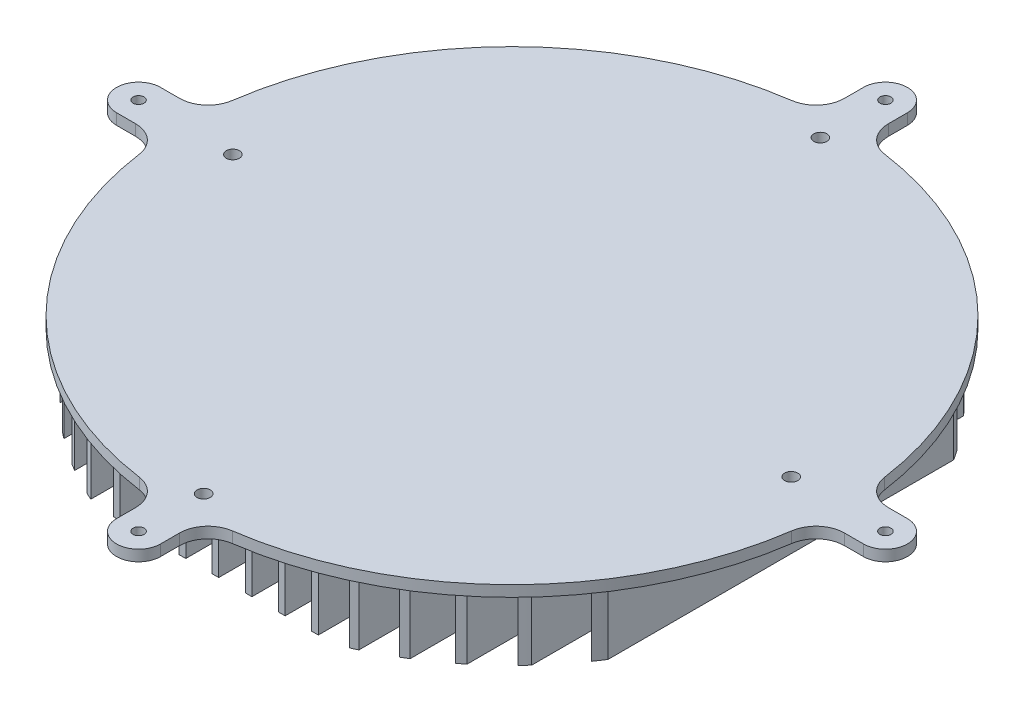
SolidWorks part; units mm, degrees
material "1060 Alloy"
ref_plane "Front Plane" through (0, 0, 0) normal (0, 0, 1) x (1, 0, 0)
ref_plane "Top Plane" through (0, 0, 0) normal (0, 1, 0) x (1, 0, 0)
ref_plane "Right Plane" through (0, 0, 0) normal (1, 0, 0) x (0, 0, -1)
sketch "Sketch3" plane through (0, 0, 0) normal (0, 1, 0) x (1, 0, 0)
  line L0 (0, 0) -> (211.9111, 0) construction
  line L1 (0, 0) -> (-205.2426, 0) construction
  line L2 (0, 0) -> (0, 170) construction
  line L3 (0, 0) -> (0, -200) construction
  line L4 (161.3691, 10) -> (170, 10)
  line L5 (161.3691, -10) -> (170, -10)
  line L6 (-10, 161.3691) -> (-10, 170)
  line L7 (10, 161.3691) -> (10, 170)
  line L8 (10, -161.3691) -> (10, -170)
  line L9 (-10, -161.3691) -> (-10, -170)
  line L10 (-161.3691, -10) -> (-170, -10)
  line L11 (-161.3691, 10) -> (-170, 10)
  arc A0 (-21.1656, 148.4992) -> (-148.4992, 21.1656) centre (0, 0) ccw
  circle A1 centre (0, 170) radius 2.5
  arc A2 (-10, 170) -> (10, 170) centre (0, 170) cw
  arc A3 (10, 161.3691) -> (21.1656, 148.4992) centre (23, 161.3691) ccw
  arc A4 (-10, 161.3691) -> (-21.1656, 148.4992) centre (-23, 161.3691) cw
  arc A5 (170, 10) -> (170, -10) centre (170, 0) cw
  arc A6 (161.3691, 10) -> (148.4992, 21.1656) centre (161.3691, 23) cw
  circle A7 centre (170, 0) radius 2.5
  arc A8 (161.3691, -10) -> (148.4992, -21.1656) centre (161.3691, -23) ccw
  arc A9 (10, -170) -> (-10, -170) centre (0, -170) cw
  arc A10 (10, -161.3691) -> (21.1656, -148.4992) centre (23, -161.3691) cw
  circle A11 centre (0, -170) radius 2.5
  arc A12 (-10, -161.3691) -> (-21.1656, -148.4992) centre (-23, -161.3691) ccw
  arc A13 (-170, -10) -> (-170, 10) centre (-170, 0) cw
  arc A14 (-161.3691, -10) -> (-148.4992, -21.1656) centre (-161.3691, -23) cw
  circle A15 centre (-170, 0) radius 2.5
  arc A16 (-161.3691, 10) -> (-148.4992, 21.1656) centre (-161.3691, 23) ccw
  arc A17 (-148.4992, -21.1656) -> (-21.1656, -148.4992) centre (0, 0) ccw
  arc A18 (148.4992, 21.1656) -> (21.1656, 148.4992) centre (0, 0) ccw
  arc A19 (21.1656, -148.4992) -> (148.4992, -21.1656) centre (0, 0) ccw
  point P53 (0, 0)
  dimension "D1" = 300
  dimension "D4" = 5
  dimension "D2" = 4
extrude "Boss-Extrude4" add sketch "Sketch3" against normal blind 5
sketch "Sketch4" plane through (0, -5, 0) normal (0, -1, 0) x (1, 0, 0)
  line L0 (0, 0) -> (0, -192.7937) construction
  line L1 (0, 0) -> (0, 216.5128) construction
  line L2 (0, 0) -> (-235.9747, 0) construction
  line L3 (0, 0) -> (242.3846, 0) construction
  line L4 (1.5, -135) -> (-1.5, -135)
  line L5 (1.5, 135) -> (-1.5, 135)
  line L6 (-1.5, -135) -> (-1.5, 135)
  line L7 (1.5, -135) -> (1.5, 135)
  line L8 (13.6111, -135) -> (13.6111, 135)
  line L9 (16.6111, -135) -> (13.6111, -135)
  line L10 (16.6111, -135) -> (16.6111, 135)
  line L11 (16.6111, 135) -> (13.6111, 135)
  line L12 (28.7222, -135) -> (28.7222, 135)
  line L13 (31.7222, -135) -> (28.7222, -135)
  line L14 (31.7222, -135) -> (31.7222, 135)
  line L15 (31.7222, 135) -> (28.7222, 135)
  line L16 (43.8333, -135) -> (43.8333, 135)
  line L17 (46.8333, -135) -> (43.8333, -135)
  line L18 (46.8333, -135) -> (46.8333, 135)
  line L19 (46.8333, 135) -> (43.8333, 135)
  line L20 (58.9444, -133.0256) -> (58.9444, 133.0256)
  line L22 (61.9444, -131.6554) -> (61.9444, 131.6554)
  line L24 (74.0556, -125.2439) -> (74.0556, 125.2439)
  line L26 (77.0556, -123.4208) -> (77.0556, 123.4208)
  line L28 (89.1667, -114.9763) -> (89.1667, 114.9763)
  line L30 (92.1667, -112.5858) -> (92.1667, 112.5858)
  line L32 (104.2778, -101.4712) -> (104.2778, 101.4712)
  line L34 (107.2778, -98.2941) -> (107.2778, 98.2941)
  line L36 (119.3889, -83.1658) -> (119.3889, 83.1658)
  line L38 (122.3889, -78.6842) -> (122.3889, 78.6842)
  line L44 (-13.5, -135) -> (-16.5, -135)
  line L45 (-13.5, -135) -> (-13.5, 135)
  line L46 (-16.5, -135) -> (-16.5, 135)
  line L47 (-13.5, 135) -> (-16.5, 135)
  line L48 (-28.5, -135) -> (-31.5, -135)
  line L49 (-28.5, -135) -> (-28.5, 135)
  line L50 (-31.5, -135) -> (-31.5, 135)
  line L51 (-28.5, 135) -> (-31.5, 135)
  line L52 (-43.5, -135) -> (-46.5, -135)
  line L53 (-43.5, -135) -> (-43.5, 135)
  line L54 (-46.5, -135) -> (-46.5, 135)
  line L55 (-43.5, 135) -> (-46.5, 135)
  line L57 (-58.5, -133.2216) -> (-58.5, 133.2216)
  line L58 (-61.5, -131.8636) -> (-61.5, 131.8636)
  line L61 (-73.5, -125.5707) -> (-73.5, 125.5707)
  line L62 (-76.5, -123.7659) -> (-76.5, 123.7659)
  line L65 (-88.5, -115.4903) -> (-88.5, 115.4903)
  line L66 (-91.5, -113.1282) -> (-91.5, 113.1282)
  line L69 (-103.5, -102.2644) -> (-103.5, 102.2644)
  line L70 (-106.5, -99.1363) -> (-106.5, 99.1363)
  line L73 (-118.5, -84.4275) -> (-118.5, 84.4275)
  line L74 (-121.5, -80.05) -> (-121.5, 80.05)
  line L80 (1.5, -135) -> (-13.5, -135) construction
  line L81 (61.9444, 135) -> (58.9444, 135) [skipped]
  line L82 (77.0556, 135) -> (74.0556, 135) [skipped]
  line L83 (92.1667, 135) -> (89.1667, 135) [skipped]
  line L84 (107.2778, 135) -> (104.2778, 135) [skipped]
  line L85 (137.5, 135) -> (134.5, 135) [skipped]
  line L86 (122.3889, 135) -> (119.3889, 135) [skipped]
  line L87 (-58.5, 135) -> (-61.5, 135) [skipped]
  line L88 (-73.5, 135) -> (-76.5, 135) [skipped]
  line L89 (-88.5, 135) -> (-91.5, 135) [skipped]
  line L90 (-103.5, 135) -> (-106.5, 135) [skipped]
  line L91 (-118.5, 135) -> (-121.5, 135) [skipped]
  line L92 (-133.5, 135) -> (-136.5, 135) [skipped]
  line L93 (-58.5, -135) -> (-61.5, -135) [skipped]
  line L94 (61.9444, -135) -> (58.9444, -135) [skipped]
  line L95 (77.0556, -135) -> (74.0556, -135) [skipped]
  line L96 (137.5, -135) -> (134.5, -135) [skipped]
  line L97 (122.3889, -135) -> (119.3889, -135) [skipped]
  line L98 (107.2778, -135) -> (104.2778, -135) [skipped]
  line L99 (92.1667, -135) -> (89.1667, -135) [skipped]
  line L100 (-133.5, -135) -> (-136.5, -135) [skipped]
  line L101 (-118.5, -135) -> (-121.5, -135) [skipped]
  line L102 (-103.5, -135) -> (-106.5, -135) [skipped]
  line L103 (-88.5, -135) -> (-91.5, -135) [skipped]
  line L104 (-73.5, -135) -> (-76.5, -135) [skipped]
  line L105 (-133.5, -57.8619) -> (-133.5, 57.8619) [skipped]
  line L106 (-136.5, -50.3786) -> (-136.5, 50.3786) [skipped]
  line L107 (134.5, -55.4977) -> (134.5, 55.4977) [skipped]
  line L108 (137.5, -47.5815) -> (137.5, 47.5815) [skipped]
  arc A3 (119.3889, -83.1658) -> (122.3889, -78.6842) centre (0, 0) ccw
  arc A4 (104.2778, -101.4712) -> (107.2778, -98.2941) centre (0, 0) ccw
  arc A5 (89.1667, -114.9763) -> (92.1667, -112.5858) centre (0, 0) ccw
  arc A6 (74.0556, -125.2439) -> (77.0556, -123.4208) centre (0, 0) ccw
  arc A7 (58.9444, -133.0256) -> (61.9444, -131.6554) centre (0, 0) ccw
  arc A8 (-76.5, -123.7659) -> (-73.5, -125.5707) centre (0, 0) ccw
  arc A9 (-61.5, -131.8636) -> (-58.5, -133.2216) centre (0, 0) ccw
  arc A10 (-91.5, -113.1282) -> (-88.5, -115.4903) centre (0, 0) ccw
  arc A11 (-106.5, -99.1363) -> (-103.5, -102.2644) centre (0, 0) ccw
  arc A12 (-121.5, -80.05) -> (-118.5, -84.4275) centre (0, 0) ccw
  arc A15 (122.3889, 78.6842) -> (119.3889, 83.1658) centre (0, 0) ccw
  arc A16 (107.2778, 98.2941) -> (104.2778, 101.4712) centre (0, 0) ccw
  arc A17 (92.1667, 112.5858) -> (89.1667, 114.9763) centre (0, 0) ccw
  arc A18 (77.0556, 123.4208) -> (74.0556, 125.2439) centre (0, 0) ccw
  arc A19 (61.9444, 131.6554) -> (58.9444, 133.0256) centre (0, 0) ccw
  arc A20 (-58.5, 133.2216) -> (-61.5, 131.8636) centre (0, 0) ccw
  arc A21 (-73.5, 125.5707) -> (-76.5, 123.7659) centre (0, 0) ccw
  arc A22 (-88.5, 115.4903) -> (-91.5, 113.1282) centre (0, 0) ccw
  arc A23 (-103.5, 102.2644) -> (-106.5, 99.1363) centre (0, 0) ccw
  arc A24 (-118.5, 84.4275) -> (-121.5, 80.05) centre (0, 0) ccw
  dimension "D1" = 135
  dimension "D2" = 1.5
  dimension "D4" = 15
  dimension "D3" = 10
extrude "Boss-Extrude5" add sketch "Sketch4" along normal blind 30
sketch "Sketch7" plane through (0, 0, 0) normal (0, 1, 0) x (1, 0, 0)
  line L0 (0, 0) -> (0, 199.2983) construction
  line L1 (180, 0) -> (-209.1437, 0) construction
  line L2 (0, 0) -> (0, -219.846) construction
  arc A0 (170, -10) -> (170, 10) centre (170, 0) ccw construction
  circle A1 centre (-127.0882, 0) radius 3
  circle A2 centre (0, 140.3779) radius 3
  circle A3 centre (0, -140.3779) radius 3
  circle A4 centre (127.0882, 0) radius 3
extrude "Cut-Extrude1" cut sketch "Sketch7" against normal blind 10
sketch "Sketch9" plane through (0, 0, 0) normal (0, 1, 0) x (1, 0, 0)
  line L0 (180, 0) -> (0, 0) construction
  line L1 (0, -180) -> (0, 180) construction
  line L8 (-10, 170) -> (-10, 161.3691)
  line L9 (-161.3691, 10) -> (-170, 10)
  line L10 (-170, -10) -> (-161.3691, -10)
  line L11 (-10, -161.3691) -> (-10, -170)
  line L12 (10, -170) -> (10, -161.3691)
  line L13 (161.3691, -10) -> (170, -10)
  line L14 (170, 10) -> (161.3691, 10)
  line L15 (10, 161.3691) -> (10, 170)
  line L16 (-10, 170) -> (-10, 161.3691)
  line L17 (-161.3691, 10) -> (-170, 10)
  line L18 (-170, -10) -> (-161.3691, -10)
  line L19 (-10, -161.3691) -> (-10, -170)
  line L20 (10, -170) -> (10, -161.3691)
  line L21 (161.3691, -10) -> (170, -10)
  line L22 (170, 10) -> (161.3691, 10)
  line L23 (10, 161.3691) -> (10, 170)
  circle A0 centre (146.1645, -33.7037) radius 12
  circle A1 centre (146.1645, 33.7037) radius 12
  circle A2 centre (-146.1645, 33.7037) radius 12
  circle A3 centre (-146.1645, -33.7037) radius 12
  circle A4 centre (-33.7037, -146.1645) radius 12
  circle A5 centre (33.7037, -146.1645) radius 12
  circle A6 centre (-146.1645, 33.7037) radius 12
  circle A7 centre (-146.1645, -33.7037) radius 12
  circle A8 centre (33.7037, 146.1645) radius 12
  circle A9 centre (-33.7037, 146.1645) radius 12
  arc A16 (10, 170) -> (-10, 170) centre (0, 170) ccw
  arc A17 (-21.1656, 148.4992) -> (-10, 161.3691) centre (-23, 161.3691) ccw
  arc A18 (-21.1656, 148.4992) -> (-148.4992, 21.1656) centre (0, 0) ccw
  arc A19 (-161.3691, 10) -> (-148.4992, 21.1656) centre (-161.3691, 23) ccw
  arc A20 (-170, 10) -> (-170, -10) centre (-170, 0) ccw
  arc A21 (-148.4992, -21.1656) -> (-161.3691, -10) centre (-161.3691, -23) ccw
  arc A22 (-148.4992, -21.1656) -> (-21.1656, -148.4992) centre (0, 0) ccw
  arc A23 (-10, -161.3691) -> (-21.1656, -148.4992) centre (-23, -161.3691) ccw
  arc A24 (-10, -170) -> (10, -170) centre (0, -170) ccw
  arc A25 (21.1656, -148.4992) -> (10, -161.3691) centre (23, -161.3691) ccw
  arc A26 (21.1656, -148.4992) -> (148.4992, -21.1656) centre (0, 0) ccw
  arc A27 (161.3691, -10) -> (148.4992, -21.1656) centre (161.3691, -23) ccw
  arc A28 (170, -10) -> (170, 10) centre (170, 0) ccw
  arc A29 (148.4992, 21.1656) -> (161.3691, 10) centre (161.3691, 23) ccw
  arc A30 (148.4992, 21.1656) -> (21.1656, 148.4992) centre (0, 0) ccw
  arc A31 (10, 161.3691) -> (21.1656, 148.4992) centre (23, 161.3691) ccw
  arc A32 (10, 170) -> (-10, 170) centre (0, 170) ccw
  arc A33 (-21.1656, 148.4992) -> (-10, 161.3691) centre (-23, 161.3691) ccw
  arc A34 (-21.1656, 148.4992) -> (-148.4992, 21.1656) centre (0, 0) ccw
  arc A35 (-161.3691, 10) -> (-148.4992, 21.1656) centre (-161.3691, 23) ccw
  arc A36 (-170, 10) -> (-170, -10) centre (-170, 0) ccw
  arc A37 (-148.4992, -21.1656) -> (-161.3691, -10) centre (-161.3691, -23) ccw
  arc A38 (-148.4992, -21.1656) -> (-21.1656, -148.4992) centre (0, 0) ccw
  arc A39 (-10, -161.3691) -> (-21.1656, -148.4992) centre (-23, -161.3691) ccw
  arc A40 (-10, -170) -> (10, -170) centre (0, -170) ccw
  arc A41 (21.1656, -148.4992) -> (10, -161.3691) centre (23, -161.3691) ccw
  arc A42 (21.1656, -148.4992) -> (148.4992, -21.1656) centre (0, 0) ccw
  arc A43 (161.3691, -10) -> (148.4992, -21.1656) centre (161.3691, -23) ccw
  arc A44 (170, -10) -> (170, 10) centre (170, 0) ccw
  arc A45 (148.4992, 21.1656) -> (161.3691, 10) centre (161.3691, 23) ccw
  arc A46 (148.4992, 21.1656) -> (21.1656, 148.4992) centre (0, 0) ccw
  arc A47 (10, 161.3691) -> (21.1656, 148.4992) centre (23, 161.3691) ccw
  point P66 (0, 0)
  dimension "D2" = 4
  dimension "D1" = 0
